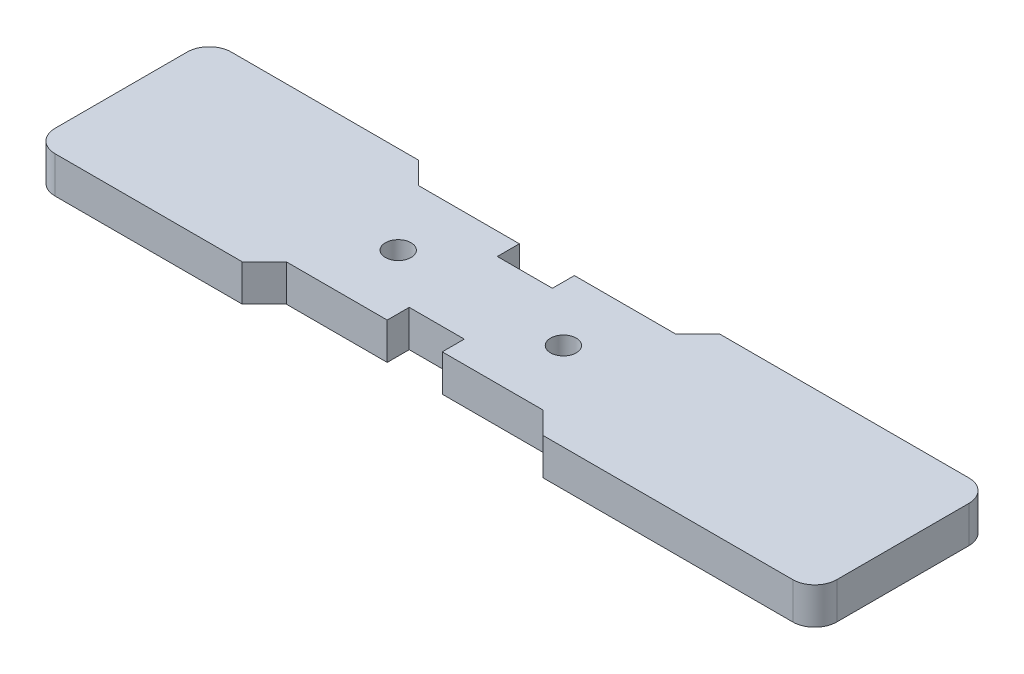
SolidWorks part; units mm, degrees
ref_plane "Front Plane" through (0, 0, 0) normal (0, 0, 1) x (1, 0, 0)
ref_plane "Top Plane" through (0, 0, 0) normal (0, 1, 0) x (1, 0, 0)
ref_plane "Right Plane" through (0, 0, 0) normal (1, 0, 0) x (0, 0, -1)
sketch "Sketch1" plane through (0, 0, 0) normal (0, 1, 0) x (1, 0, 0)
  line L1 (0, 12) -> (57.5, 12)
  line L2 (57.5, 12) -> (57.5, -12)
  line L3 (57.5, -12) -> (0, -12)
  line L4 (-49, -12) -> (-49, 12)
  line L5 (-49, 12) -> (0, 12)
  line L7 (0, -12) -> (-49, -12)
  line L8 (0, 12) -> (0, -12) construction
  point P5 (0, 0)
  dimension "D1" = 24
  dimension "D2" = 57.5
  dimension "D3" = 49
extrude "Boss-Extrude1" add sketch "Sketch1" along normal blind 5
sketch "Sketch5" plane through (0, 0, 0) normal (0, 1, 0) x (1, 0, 0)
  line L2 (-49, 12) -> (-49, -12) construction
  line L5 (57.5, -12) -> (57.5, 12) construction
  circle A0 centre (-37, 0) radius 5
  circle A1 centre (45.5, 0) radius 5
  dimension "D1" = 10
  dimension "D3" = 12
  dimension "D2" = 12
extrude "Boss-Extrude2" add sketch "Sketch5" against normal blind 4
sketch "Sketch7" plane through (0, 0, 0) normal (0, -1, 0) x (1, 0, 0)
  line L0 (17.5, 12) -> (-17.5, 12)
  line L1 (-49, 12) -> (57.5, 12) construction
  line L2 (-17.5, 12) -> (-17.5, 9)
  line L3 (-17.5, 9) -> (17.5, 9)
  line L4 (17.5, 9) -> (17.5, 12)
  line L5 (2.75, 0) -> (-2.75, 0) construction
  line L6 (17.5, -9) -> (17.5, -12)
  line L7 (-17.5, -9) -> (17.5, -9)
  line L8 (-17.5, -12) -> (-17.5, -9)
  line L9 (17.5, -12) -> (-17.5, -12)
  point P7 (0, 9)
  point P16 (0, -9)
  dimension "D1" = 3
  dimension "D2" = 35
extrude "Cut-Extrude2" cut sketch "Sketch7" against normal through all
sketch "Sketch6" plane through (0, 0, 0) normal (0, -1, 0) x (1, 0, 0)
  line L0 (3.75, 9) -> (-3.75, 9)
  line L2 (-3.75, 9) -> (-3.75, 6)
  line L3 (-3.75, 6) -> (3.75, 6)
  line L4 (3.75, 6) -> (3.75, 9)
  line L6 (2.75, 0) -> (-2.75, 0) construction
  line L7 (-3.75, -6) -> (3.75, -6)
  line L8 (-3.75, -9) -> (-3.75, -6)
  line L9 (3.75, -9) -> (-3.75, -9)
  line L10 (3.75, -6) -> (3.75, -9)
  line L11 (-17.5, 9) -> (17.5, 9) construction
  point P4 (0, 9)
  point P7 (0, 9)
  point P16 (-33.75, -12)
  dimension "D1" = 3
  dimension "D2" = 7.5
extrude "Cut-Extrude1" cut sketch "Sketch6" against normal through all
sketch "Sketch8" plane through (0, 0, 0) normal (0, -1, 0) x (1, 0, 0)
  line L0 (-49, 0) -> (57.5, 0) construction
  line L1 (-3.75, -6) -> (-3.75, -9) construction
  line L2 (57.5, 12) -> (57.5, -12) construction
  line L3 (0, -4.95) -> (0, 4.95) construction
  line L4 (-49, -12) -> (-49, 12) construction
  circle A0 centre (-11.25, 0) radius 1.75
  circle A4 centre (11.25, 0) radius 1.75
  dimension "D1" = 3.5
  dimension "D2" = 7.5
extrude "Cut-Extrude3" cut sketch "Sketch8" against normal through all
fillet "Fillet3" radius 3 4 edges at (57.5, 2.5, -12) (57.5, 2.5, 12) (-49, 2.5, -12) (-49, 2.5, 12)
fillet "Fillet2" radius 0.25 2 edges at (-37, -4, 5) (45.5, -4, -5)
chamfer "Chamfer1" distance 3 angle 45 4 edges at (17.5, 2.5, -12) (-17.5, 2.5, -12) (17.5, 2.5, 12) (-17.5, 2.5, 12)
